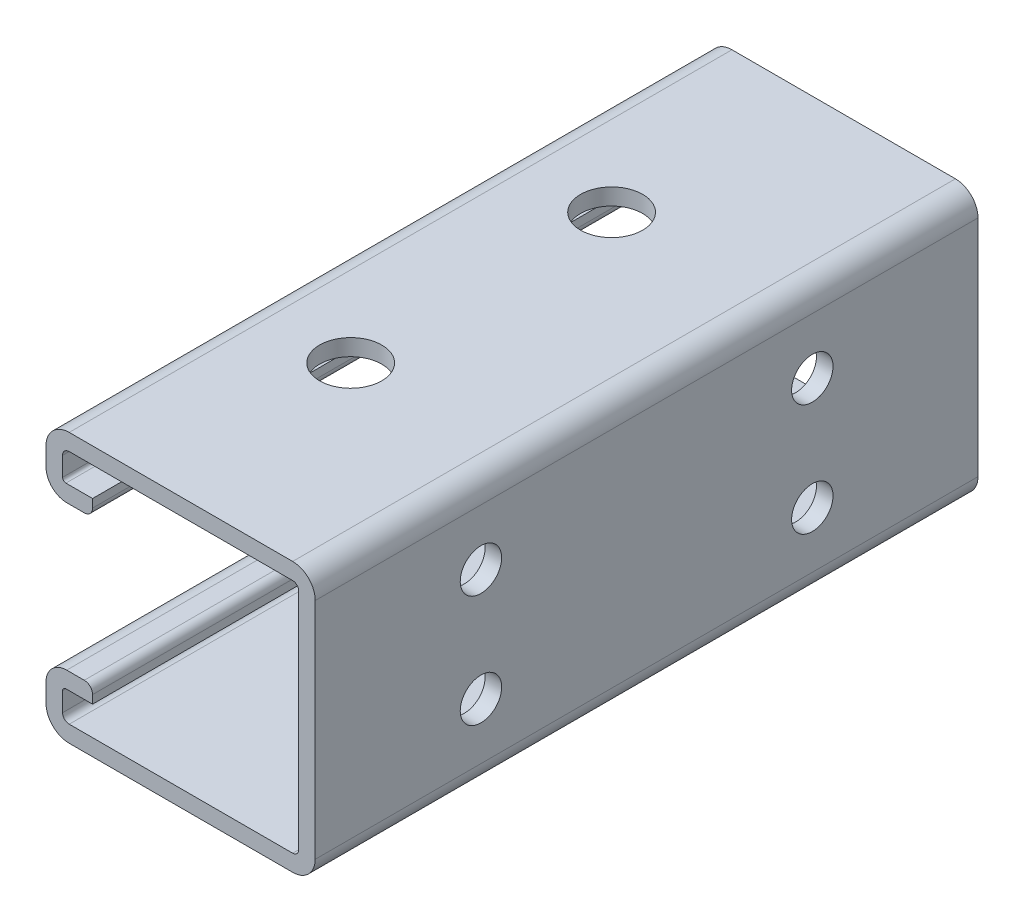
SolidWorks part; units mm, degrees
ref_plane "Front Plane" through (0, 0, 0) normal (0, 0, 1) x (1, 0, 0)
ref_plane "Top Plane" through (0, 0, 0) normal (0, 1, 0) x (1, 0, 0)
ref_plane "Right Plane" through (0, 0, 0) normal (1, 0, 0) x (0, 0, -1)
sketch "Sketch1" plane through (0, 0, 0) normal (0, 0, 1) x (1, 0, 0)
  line L0 (20.6375, 0) -> (-20.6375, 0) construction
  line L3 (-20.6375, 20.6375) -> (20.6375, 20.6375) construction
  line L4 (-20.6375, 20.6375) -> (-20.6375, -20.6375) construction
  line L5 (-20.6375, -20.6375) -> (20.6375, -20.6375) construction
  line L6 (20.6375, 20.6375) -> (20.6375, -20.6375) construction
  line L7 (-17.0815, 20.6375) -> (17.1768, 20.6375)
  line L8 (20.6375, 17.1767) -> (20.6375, -17.1767)
  line L9 (18.0975, -17.1767) -> (18.0975, 17.1767)
  line L10 (17.1768, 18.0975) -> (-17.0815, 18.0975)
  line L11 (-20.6375, 17.0815) -> (-20.6375, 14.2875)
  line L12 (-17.4625, 11.1125) -> (-14.7701, 11.1125)
  line L14 (-13.5001, 13.6525) -> (-17.5895, 13.6525)
  line L15 (-18.0975, 14.1605) -> (-18.0975, 17.0815)
  line L16 (-18.0975, -14.1605) -> (-18.0975, -17.0815)
  line L17 (-13.5001, -13.6525) -> (-17.5895, -13.6525)
  line L18 (-17.4625, -11.1125) -> (-14.7701, -11.1125)
  line L19 (-20.6375, -17.0815) -> (-20.6375, -14.2875)
  line L20 (17.1768, -18.0975) -> (-17.0815, -18.0975)
  line L21 (-17.0815, -20.6375) -> (17.1768, -20.6375)
  line L22 (18.0975, -20.6375) -> (18.0975, 20.6375) construction
  line L23 (-13.5001, 13.6525) -> (-13.5001, 12.3825)
  line L24 (-13.5001, 12.3825) -> (-13.5001, 11.1125) construction
  line L25 (-13.5001, -13.6525) -> (-13.5001, -12.3825)
  line L26 (0.0476, 18.0975) -> (0.0476, -18.0975) construction
  arc A1 (20.6375, 17.1767) -> (17.1768, 20.6375) centre (17.1768, 17.1767) ccw
  arc A2 (18.0975, 17.1767) -> (17.1768, 18.0975) centre (17.1768, 17.1767) ccw
  arc A4 (-17.0815, 20.6375) -> (-20.6375, 17.0815) centre (-17.0815, 17.0815) ccw
  arc A5 (-20.6375, 14.2875) -> (-17.4625, 11.1125) centre (-17.4625, 14.2875) ccw
  arc A6 (-13.5001, 12.3825) -> (-14.7701, 11.1125) centre (-14.7701, 12.3825) cw
  arc A7 (-17.5895, 13.6525) -> (-18.0975, 14.1605) centre (-17.5895, 14.1605) cw
  arc A8 (-18.0975, 17.0815) -> (-17.0815, 18.0975) centre (-17.0815, 17.0815) cw
  arc A9 (-18.0975, -17.0815) -> (-17.0815, -18.0975) centre (-17.0815, -17.0815) ccw
  arc A10 (-17.5895, -13.6525) -> (-18.0975, -14.1605) centre (-17.5895, -14.1605) ccw
  arc A11 (-13.5001, -12.3825) -> (-14.7701, -11.1125) centre (-14.7701, -12.3825) ccw
  arc A12 (-20.6375, -14.2875) -> (-17.4625, -11.1125) centre (-17.4625, -14.2875) cw
  arc A13 (-17.0815, -20.6375) -> (-20.6375, -17.0815) centre (-17.0815, -17.0815) cw
  arc A14 (18.0975, -17.1767) -> (17.1768, -18.0975) centre (17.1768, -17.1767) cw
  arc A15 (20.6375, -17.1767) -> (17.1768, -20.6375) centre (17.1768, -17.1767) cw
  point P24 (20.6375, 20.6375)
  point P65 (18.0975, 0)
  dimension "D1" = 3.4608
  dimension "D2" = 3.556
  dimension "D3" = 3.175
  dimension "D5" = 0.508
  dimension "Channel Height" = 41.275
  dimension "Channel Width" = 41.275
  dimension "Thickness" = 2.54
  dimension "Inside Channel Width" = 22.225
  dimension "D4" = 7.1374
  dimension "D6" = 2.54
  dimension "D7" = 3.5814
  dimension "D8" = 36.195
sketch "Sketch3" plane through (0, 0, 0) normal (1, 0, 0) x (0, 0, -1)
  line L0 (-152.4, 0) -> (152.4, 0) construction
  point P2 (-69.85, 0)
  point P3 (69.85, 0)
  dimension "D1" = 82.55
  dimension "D2" = 82.55
  dimension "Length" = 304.8
sketch "Sketch4" plane through (0, 0, 0) normal (0, 0, 1) x (1, 0, 0)
  line L16 (-17.0815, -20.6375) -> (17.1768, -20.6375)
  line L17 (-20.6375, -14.2875) -> (-20.6375, -17.0815)
  line L18 (-14.7701, -11.1125) -> (-17.4625, -11.1125)
  line L19 (-13.5001, -13.6525) -> (-13.5001, -12.3825)
  line L20 (-17.5895, -13.6525) -> (-13.5001, -13.6525)
  line L21 (-18.0975, -17.0815) -> (-18.0975, -14.1605)
  line L22 (17.1768, -18.0975) -> (-17.0815, -18.0975)
  line L23 (18.0975, 17.1767) -> (18.0975, -17.1767)
  line L24 (-17.0815, 18.0975) -> (17.1768, 18.0975)
  line L25 (-18.0975, 14.1605) -> (-18.0975, 17.0815)
  line L26 (-13.5001, 13.6525) -> (-17.5895, 13.6525)
  line L27 (-13.5001, 12.3825) -> (-13.5001, 13.6525)
  line L28 (-17.4625, 11.1125) -> (-14.7701, 11.1125)
  line L29 (-20.6375, 17.0815) -> (-20.6375, 14.2875)
  line L30 (17.1768, 20.6375) -> (-17.0815, 20.6375)
  line L31 (20.6375, -17.1767) -> (20.6375, 17.1767)
  line L32 (-17.0815, -20.6375) -> (17.1768, -20.6375)
  line L33 (-20.6375, -14.2875) -> (-20.6375, -17.0815)
  line L34 (-14.7701, -11.1125) -> (-17.4625, -11.1125)
  line L35 (-13.5001, -13.6525) -> (-13.5001, -12.3825)
  line L36 (-17.5895, -13.6525) -> (-13.5001, -13.6525)
  line L37 (-18.0975, -17.0815) -> (-18.0975, -14.1605)
  line L38 (17.1768, -18.0975) -> (-17.0815, -18.0975)
  line L39 (18.0975, 17.1767) -> (18.0975, -17.1767)
  line L40 (-17.0815, 18.0975) -> (17.1768, 18.0975)
  line L41 (-18.0975, 14.1605) -> (-18.0975, 17.0815)
  line L42 (-13.5001, 13.6525) -> (-17.5895, 13.6525)
  line L43 (-13.5001, 12.3825) -> (-13.5001, 13.6525)
  line L44 (-17.4625, 11.1125) -> (-14.7701, 11.1125)
  line L45 (-20.6375, 17.0815) -> (-20.6375, 14.2875)
  line L46 (17.1768, 20.6375) -> (-17.0815, 20.6375)
  line L47 (20.6375, -17.1767) -> (20.6375, 17.1767)
  arc A14 (-20.6375, -17.0815) -> (-17.0815, -20.6375) centre (-17.0815, -17.0815) ccw
  arc A15 (-17.4625, -11.1125) -> (-20.6375, -14.2875) centre (-17.4625, -14.2875) ccw
  arc A16 (-13.5001, -12.3825) -> (-14.7701, -11.1125) centre (-14.7701, -12.3825) ccw
  arc A17 (-17.5895, -13.6525) -> (-18.0975, -14.1605) centre (-17.5895, -14.1605) ccw
  arc A18 (-18.0975, -17.0815) -> (-17.0815, -18.0975) centre (-17.0815, -17.0815) ccw
  arc A19 (17.1768, -18.0975) -> (18.0975, -17.1767) centre (17.1768, -17.1767) ccw
  arc A20 (18.0975, 17.1767) -> (17.1768, 18.0975) centre (17.1768, 17.1767) ccw
  arc A21 (-17.0815, 18.0975) -> (-18.0975, 17.0815) centre (-17.0815, 17.0815) ccw
  arc A22 (-18.0975, 14.1605) -> (-17.5895, 13.6525) centre (-17.5895, 14.1605) ccw
  arc A23 (-14.7701, 11.1125) -> (-13.5001, 12.3825) centre (-14.7701, 12.3825) ccw
  arc A24 (-20.6375, 14.2875) -> (-17.4625, 11.1125) centre (-17.4625, 14.2875) ccw
  arc A25 (-17.0815, 20.6375) -> (-20.6375, 17.0815) centre (-17.0815, 17.0815) ccw
  arc A26 (20.6375, 17.1767) -> (17.1768, 20.6375) centre (17.1768, 17.1767) ccw
  arc A27 (17.1768, -20.6375) -> (20.6375, -17.1767) centre (17.1768, -17.1767) ccw
  arc A28 (-20.6375, -17.0815) -> (-17.0815, -20.6375) centre (-17.0815, -17.0815) ccw
  arc A29 (-17.4625, -11.1125) -> (-20.6375, -14.2875) centre (-17.4625, -14.2875) ccw
  arc A30 (-13.5001, -12.3825) -> (-14.7701, -11.1125) centre (-14.7701, -12.3825) ccw
  arc A31 (-17.5895, -13.6525) -> (-18.0975, -14.1605) centre (-17.5895, -14.1605) ccw
  arc A32 (-18.0975, -17.0815) -> (-17.0815, -18.0975) centre (-17.0815, -17.0815) ccw
  arc A33 (17.1768, -18.0975) -> (18.0975, -17.1767) centre (17.1768, -17.1767) ccw
  arc A34 (18.0975, 17.1767) -> (17.1768, 18.0975) centre (17.1768, 17.1767) ccw
  arc A35 (-17.0815, 18.0975) -> (-18.0975, 17.0815) centre (-17.0815, 17.0815) ccw
  arc A36 (-18.0975, 14.1605) -> (-17.5895, 13.6525) centre (-17.5895, 14.1605) ccw
  arc A37 (-14.7701, 11.1125) -> (-13.5001, 12.3825) centre (-14.7701, 12.3825) ccw
  arc A38 (-20.6375, 14.2875) -> (-17.4625, 11.1125) centre (-17.4625, 14.2875) ccw
  arc A39 (-17.0815, 20.6375) -> (-20.6375, 17.0815) centre (-17.0815, 17.0815) ccw
  arc A40 (20.6375, 17.1767) -> (17.1768, 20.6375) centre (17.1768, 17.1767) ccw
  arc A41 (17.1768, -20.6375) -> (20.6375, -17.1767) centre (17.1768, -17.1767) ccw
  dimension "D1" = 0
extrude "Boss-Extrude1" add sketch "Sketch4" along normal blind 50.8 and the other way blind 50.8
sketch "Sketch7" plane through (0, 20.6375, 0) normal (0, 1, 0) x (1, 0, 0)
  line L0 (17.1768, 0) -> (-17.0815, 0) construction
  line L1 (17.1768, 50.8) -> (17.1768, -50.8) construction
  line L2 (-17.0815, 50.8) -> (-17.0815, -50.8) construction
  line L3 (0.0476, 50.8) -> (0.0476, -50.8) construction
  line L4 (17.1768, 50.8) -> (-17.0815, 50.8) construction
  line L5 (17.1768, -50.8) -> (-17.0815, -50.8) construction
  circle A0 centre (-4.7307, -20) radius 4.7625
  circle A1 centre (-4.7308, 20) radius 4.7625
  point P6 (-4.7307, -20)
  dimension "D3" = 9.525
  dimension "D1" = 20
  dimension "D2" = 21.9075
extrude "Cut-Extrude1" cut sketch "Sketch7" against normal blind 45.72
sketch "Sketch8" plane through (20.6375, 0, 0) normal (1, 0, 0) x (0, 0, -1)
  line L0 (0, 0) -> (0, -17.1767) construction
  line L1 (-50.8, -17.1767) -> (50.8, -17.1767) construction
  line L2 (-50.8, -17.1767) -> (-50.8, 17.1767) construction
  line L3 (-50.8, 17.1767) -> (50.8, 17.1767) construction
  line L4 (50.8, -17.1767) -> (50.8, 17.1767) construction
  line L5 (-50.8, -17.1767) -> (50.8, 17.1767) construction
  line L6 (-50.8, 17.1767) -> (50.8, -17.1767) construction
  line L7 (0, 0) -> (50.8, 0) construction
  line L8 (25.4, 0) -> (25.4, -17.1767) construction
  line L9 (0, -8.5884) -> (50.8, -8.5884) construction
  circle A0 centre (25.4, -8.5884) radius 3.175
  circle A1 centre (25.4, 8.5884) radius 3.175
  circle A2 centre (-25.4, -8.5884) radius 3.175
  circle A3 centre (-25.4, 8.5884) radius 3.175
  point P0 (0, 0)
  dimension "D1" = 6.35
  dimension "D2" = 34.3535
extrude "Cut-Extrude2" cut sketch "Sketch8" against normal up to surface (2.54 mm away) up to face at (18.0975, 0, 0)
equation "\"D1@Sketch3\" = \"Channel Height@Sketch1\" * 2"
equation "\"D2@Sketch3\"=\"D1@Sketch3\""
equation "\"D6@Sketch1\"=\"Thickness@Sketch1\""
